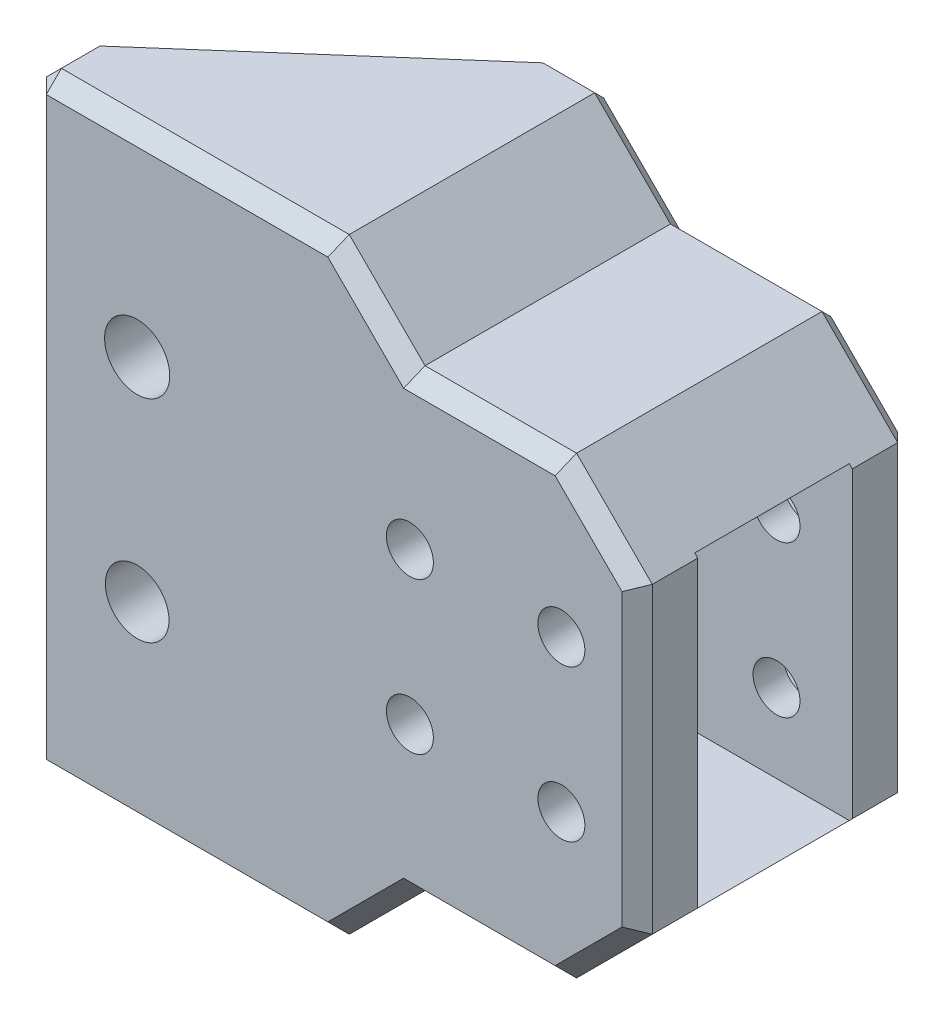
SolidWorks part; units mm, degrees
material "ABS"
ref_plane "前视基准面" through (0, 0, 0) normal (0, 0, 1) x (1, 0, 0)
ref_plane "上视基准面" through (0, 0, 0) normal (0, 1, 0) x (1, 0, 0)
ref_plane "右视基准面" through (0, 0, 0) normal (1, 0, 0) x (0, 0, -1)
other "Configuration Table"
sketch "草图1" plane through (0, 0, 0) normal (0, 0, 1) x (1, 0, 0)
  line L0 (0, 15) -> (40, 15) construction
  line L1 (0, 0) -> (40, 0)
  line L2 (0, 0) -> (0, 30)
  line L3 (0, 30) -> (40, 30)
  line L4 (40, 0) -> (40, 30)
  circle A0 centre (7, 22) radius 2.15
  circle A1 centre (7, 8) radius 2.1
  circle A2 centre (35, 20) radius 1.55
  circle A3 centre (25, 20) radius 1.55
  circle A4 centre (25, 10) radius 1.55
  circle A5 centre (35, 10) radius 1.55
  point P9 (0, 15)
  dimension "D5" = 4.3
  dimension "D6" = 4.2
  dimension "D9" = 3.1
  dimension "D1" = 30
  dimension "D2" = 40
  dimension "D3" = 7
  dimension "D4" = 7
  dimension "D7" = 7
  dimension "D8" = 7
  dimension "D10" = 5
  dimension "D11" = 5
  dimension "D12" = 2
  dimension "D13" = 2
extrude "凸台-拉伸1" add sketch "草图1" along normal blind 4
chamfer "倒角1" distance 5 angle 45 2 edges at (40, 0, 2) (40, 30, 2)
sketch "草图3" plane through (0, 0, 0) normal (0, 0, -1) x (-1, 0, 0)
  line L0 (-40, 5) -> (-40, 25) construction
  line L1 (-40, 25) -> (-20, 25)
  line L3 (-40, 5) -> (-20, 5)
  line L4 (-20, 25) -> (-20, 5)
  line L5 (-40, 25) -> (-35, 30)
  line L6 (-35, 30) -> (-16.2, 30)
  line L7 (-35, 30) -> (0, 30) construction
  line L8 (-16.2, 30) -> (-16.2, 0)
  line L9 (0, 0) -> (-35, 0) construction
  line L10 (-16.2, 0) -> (-35, 0)
  line L11 (-35, 0) -> (-40, 5)
  line L12 (0, 30) -> (0, 0) construction
  circle A0 centre (-25, 20) radius 1.55 construction
  circle A1 centre (-25, 10) radius 1.55 construction
  dimension "D1" = 5
  dimension "D2" = 5
  dimension "D3" = 5
  dimension "D4" = 16.2
extrude "凸台-拉伸2" add sketch "草图3" along normal blind 10.2
sketch "草图4" plane through (0, 0, -10.2) normal (0, 0, -1) x (-1, 0, 0)
  line L0 (-40, 25) -> (-40, 5)
  line L1 (-40, 5) -> (-35, 0)
  line L2 (-35, 0) -> (-16.2, 0)
  line L3 (-16.2, 0) -> (-16.2, 30)
  line L4 (-16.2, 30) -> (-35, 30)
  line L5 (-35, 30) -> (-40, 25)
  circle A0 centre (-35, 20) radius 1.55
  circle A1 centre (-25, 20) radius 1.55
  circle A2 centre (-25, 10) radius 1.55
  circle A3 centre (-35, 10) radius 1.55
extrude "凸台-拉伸3" add sketch "草图4" along normal blind 4
chamfer "倒角2" [suppressed] distance 5 angle 45
sketch "草图7" plane through (0, 0, 0) normal (0, -1, 0) x (1, 0, 0)
  line L0 (0, 0) -> (16.2, -14.2)
  line L1 (16.2, -14.2) -> (30, -14.2)
  line L2 (35, -14.2) -> (16.2, -14.2) construction
  line L3 (30, -14.2) -> (30, 4)
  line L4 (0, 4) -> (35, 4) construction
  line L5 (30, 4) -> (0, 4)
  line L6 (0, 4) -> (0, 0)
  line L7 (35, -14.2) -> (35, 4) construction
  dimension "D1" = 5
extrude "凸台-拉伸4" add sketch "草图7" along normal blind 5
sketch "草图8" plane through (0, 30, 0) normal (0, 1, 0) x (1, 0, 0)
  line L0 (0, 0) -> (16.2, 14.2)
  line L1 (16.2, 14.2) -> (30, 14.2)
  line L2 (30, 14.2) -> (30, -4)
  line L3 (35, -4) -> (0, -4) construction
  line L4 (30, -4) -> (0, -4)
  line L5 (0, -4) -> (0, 0)
  line L6 (35, -4) -> (35, 14.2) construction
  point P0 (0, 0)
  point P3 (0.0366, 0.0321)
  dimension "D1" = 5
extrude "凸台-拉伸5" add sketch "草图8" along normal blind 5
chamfer "倒角3" distance 10 angle 45 2 edges at (30, 35, -5.1) (30, -5, -5.1)
chamfer "倒角4" distance 1 angle 45 25 edges at (8.1, 30, -7.1) (8.1, 0, -7.1) (22.5, 32.5, 4) (10, 35, 4) (0, 15, 4) (0, 35, 2) (30, 30, 4) (37.5, 27.5, 4) (40, 15, 4) (37.5, 2.5, 4) (30, 0, 4) (22.5, -2.5, 4) (10, -5, 4) (0, -5, 2) (8.1, 35, -7.1) (8.1, -5, -7.1) (18.1, 35, -14.2) (22.5, 32.5, -14.2) (30, 30, -14.2) (37.5, 27.5, -14.2) (40, 15, -14.2) (18.1, -5, -14.2) (22.5, -2.5, -14.2) (30, 0, -14.2) (37.5, 2.5, -14.2)
sketch "草图9" plane through (0, 0, -14.2) normal (0, 0, -1) x (-1, 0, 0)
  line L1 (-35, 16.7668) -> (-32.2, 18.3834)
  line L2 (-32.2, 18.3834) -> (-32.2, 21.6166)
  line L3 (-32.2, 21.6166) -> (-35, 23.2332)
  line L4 (-35, 23.2332) -> (-37.8, 21.6166)
  line L5 (-37.8, 21.6166) -> (-37.8, 18.3834)
  line L6 (-37.8, 18.3834) -> (-35, 16.7668)
  line L12 (26.2459, 18.7199) -> (29.0459, 20.3364)
  line L13 (29.0459, 20.3364) -> (29.0459, 23.5696)
  line L14 (29.0459, 23.5696) -> (26.2459, 25.1862)
  line L15 (26.2459, 25.1862) -> (23.4459, 23.5696)
  line L16 (23.4459, 23.5696) -> (23.4459, 20.3364)
  line L17 (23.4459, 20.3364) -> (26.2459, 18.7199)
  line L25 (-35, 6.7668) -> (-32.2, 8.3834)
  line L26 (-32.2, 8.3834) -> (-32.2, 11.6166)
  line L27 (-32.2, 11.6166) -> (-35, 13.2332)
  line L28 (-35, 13.2332) -> (-37.8, 11.6166)
  line L29 (-37.8, 11.6166) -> (-37.8, 8.3834)
  line L30 (-37.8, 8.3834) -> (-35, 6.7668)
  line L31 (-25, 6.7668) -> (-22.2, 8.3834)
  line L32 (-22.2, 8.3834) -> (-22.2, 11.6166)
  line L33 (-22.2, 11.6166) -> (-25, 13.2332)
  line L34 (-25, 13.2332) -> (-27.8, 11.6166)
  line L35 (-27.8, 11.6166) -> (-27.8, 8.3834)
  line L36 (-27.8, 8.3834) -> (-25, 6.7668)
  line L37 (-25, 16.7668) -> (-22.2, 18.3834)
  line L38 (-22.2, 18.3834) -> (-22.2, 21.6166)
  line L39 (-22.2, 21.6166) -> (-25, 23.2332)
  line L40 (-25, 23.2332) -> (-27.8, 21.6166)
  line L41 (-27.8, 21.6166) -> (-27.8, 18.3834)
  line L42 (-27.8, 18.3834) -> (-25, 16.7668)
  circle A0 centre (-35, 20) radius 2.8 construction
  circle A2 centre (26.2459, 21.953) radius 2.8 construction
  circle A4 centre (-35, 10) radius 2.8 construction
  circle A5 centre (-25, 10) radius 2.8 construction
  circle A6 centre (-25, 20) radius 2.8 construction
  dimension "D1" = 5.6
  dimension "D2" = 5.6
  dimension "D3" = 5.6
  dimension "D4" = 5.6
extrude "切除-拉伸1" cut sketch "草图9" against normal blind 2
sketch "草图10" plane through (20, 0, 0) normal (1, 0, 0) x (0, 0, -1)
  line L0 (0, 25) -> (0, 5) construction
  line L6 (0, 25.2) -> (10.2, 25.2)
  line L7 (0, 25.2) -> (0, 4.8)
  line L9 (0, 4.8) -> (10.2, 4.8)
  line L10 (10.2, 25.2) -> (10.2, 4.8)
  line L11 (10.2, 25) -> (10.2, 5) construction
  line L12 (10.2, 25) -> (0, 25) construction
  line L13 (10.2, 5) -> (0, 5) construction
  point P7 (10.2, 23.2047)
  dimension "D1" = 0.2
  dimension "D2" = 0.2
extrude "切除-拉伸2" cut sketch "草图10" along normal through all
